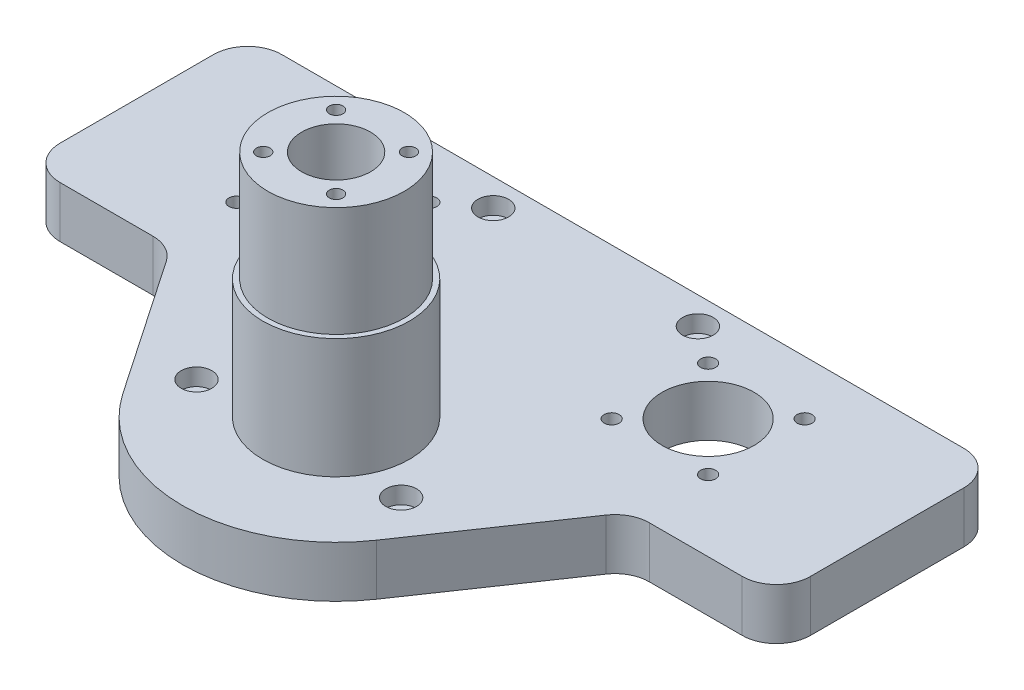
SolidWorks part; units mm, degrees
material "PLA Infill"
ref_plane "Front Plane" through (0, 0, 0) normal (0, 0, 1) x (1, 0, 0)
ref_plane "Top Plane" through (0, 0, 0) normal (0, 1, 0) x (1, 0, 0)
ref_plane "Right Plane" through (0, 0, 0) normal (1, 0, 0) x (0, 0, -1)
sketch "Sketch1" plane through (0, 0, 0) normal (0, 1, 0) x (1, 0, 0)
  line L0 (0, 0) -> (55, 54.0672) construction
  line L1 (55, 54.0672) -> (-55, 54.0672) construction
  line L2 (-55, 54.0672) -> (0, 0) construction
  line L3 (-79.7903, 37.1722) -> (-37.1854, -25.3425) construction
  line L4 (-55, 84.0672) -> (55, 84.0672)
  line L5 (37.1854, -25.3425) -> (79.7903, 37.1722) construction
  line L6 (-55, 84.0672) -> (-100, 84.0672)
  line L7 (-110, 74.0672) -> (-110, 29.0672)
  line L8 (-100, 19.0672) -> (-72.7378, 19.0672)
  line L9 (-64.4743, 14.6989) -> (-37.1854, -25.3425)
  line L10 (0, -1000) -> (0, 49000) construction
  line L11 (64.4743, 14.6989) -> (37.1854, -25.3425)
  line L12 (100, 19.0672) -> (72.7378, 19.0672)
  line L13 (110, 74.0672) -> (110, 29.0672)
  line L14 (55, 84.0672) -> (100, 84.0672)
  circle A0 centre (-55, 54.0672) radius 30 construction
  circle A1 centre (55, 54.0672) radius 30 construction
  circle A2 centre (0, 0) radius 45 construction
  arc A3 (-79.7903, 37.1722) -> (-55, 84.0672) centre (-55, 54.0672) cw construction
  arc A4 (55, 84.0672) -> (79.7903, 37.1722) centre (55, 54.0672) cw construction
  arc A5 (-37.1854, -25.3425) -> (37.1854, -25.3425) centre (0, 0) ccw
  arc A6 (-72.7378, 19.0672) -> (-64.4743, 14.6989) centre (-72.7378, 9.0672) cw
  arc A7 (-110, 29.0672) -> (-100, 19.0672) centre (-100, 29.0672) ccw
  arc A8 (-100, 84.0672) -> (-110, 74.0672) centre (-100, 74.0672) ccw
  arc A9 (72.7378, 19.0672) -> (64.4743, 14.6989) centre (72.7378, 9.0672) ccw
  arc A10 (110, 29.0672) -> (100, 19.0672) centre (100, 29.0672) cw
  arc A11 (100, 84.0672) -> (110, 74.0672) centre (100, 74.0672) cw
  point P23 (-67.4514, 19.0672)
  dimension "D3" = 60
  dimension "D4" = 90
  dimension "D5" = 10
  dimension "D6" = 55
  dimension "D1" = 110
  dimension "D2" = 77.125
  dimension "D7" = 35
extrude "Main Body" add sketch "Sketch1" along normal blind 15 contours A5 L11 A9 L12 A10 L13 A11 L14 L4 L6 A8 L7 A7 L8 A6 L9
sketch "Sketch3" plane through (0, 15, 0) normal (0, 1, 0) x (1, 0, 0)
  circle A0 centre (0, 0) radius 45 construction
  circle A1 centre (0, 0) radius 45 construction
  circle A2 centre (0, 0) radius 21.5
  dimension "D1" = 43
extrude "Front Extrusion" add sketch "Sketch3" along normal blind 67.3
sketch "Sketch4" plane through (0, 0, 0) normal (0, -1, 0) x (1, 0, 0)
  line L0 (0, -1000) -> (0, 49000) construction
  line L1 (-45, 0) -> (45, 0) construction
  line L2 (-85, -54.0672) -> (-25, -54.0672) construction
  line L3 (55, -54.0672) -> (-55, -54.0672) construction
  line L4 (-55, -24.0672) -> (-55, -84.0672) construction
  line L5 (-10.6773, 10.6773) -> (0, 0) construction
  line L6 (-10.6773, -10.6773) -> (0, 0) construction
  line L7 (-69.1421, -39.9251) -> (-55, -54.0672) construction
  line L8 (-100, -84.0672) -> (100, -84.0672) construction
  line L9 (100, -84.0672) -> (-100, -84.0672) construction
  line L10 (-30, -76.0672) -> (0, -76.0672) construction
  line L11 (-30, -76.0672) -> (-30, 10.9328) construction
  line L12 (-30, 10.9328) -> (0, 10.9328) construction
  line L13 (0, -76.0672) -> (0, 10.9328) construction
  circle A0 centre (55, -54.0672) radius 30 construction
  circle A1 centre (0, 0) radius 45 construction
  circle A2 centre (-55, -54.0672) radius 30 construction
  circle A3 centre (55, -54.0672) radius 30 construction
  circle A4 centre (0, 0) radius 45 construction
  circle A5 centre (-55, -54.0672) radius 30 construction
  circle A6 centre (0, 0) radius 10.1
  circle A7 centre (-55, -54.0672) radius 13.5
  circle A10 centre (-10.6773, 10.6773) radius 2
  circle A13 centre (-10.6773, -10.6773) radius 2
  circle A14 centre (-69.1421, -39.9251) radius 2.2
  circle A15 centre (-69.1421, -68.2094) radius 2.2
  circle A16 centre (-40.8579, -68.2094) radius 2.2
  circle A17 centre (-40.8579, -39.9251) radius 2.2
  circle A18 centre (55, -54.0672) radius 13.5
  circle A19 centre (69.1421, -68.2094) radius 2.2
  circle A20 centre (40.8579, -68.2094) radius 2.2
  circle A21 centre (40.8579, -39.9251) radius 2.2
  circle A22 centre (69.1421, -39.9251) radius 2.2
  circle A23 centre (10.6773, -10.6773) radius 2
  circle A24 centre (10.6773, 10.6773) radius 2
  circle A25 centre (-30, -76.0672) radius 2.5
  circle A26 centre (-30, 10.9328) radius 2.5
  circle A27 centre (30, -76.0672) radius 2.5
  circle A28 centre (30, 10.9328) radius 2.5
  dimension "D1" = 20.2
  dimension "D2" = 27
  dimension "D4" = 4
  dimension "D5" = 45
  dimension "D7" = 4.4
  dimension "D9" = 5
  dimension "D3" = 15.1
  dimension "D6" = 20
  dimension "D8" = 45
  dimension "D10" = 30
  dimension "D11" = 8
  dimension "D12" = 87
extrude "Bolt Holes" cut sketch "Sketch4" against normal through all
sketch "Sketch5" plane through (0, 0, 0) normal (0, -1, 0) x (1, 0, 0)
  line L0 (-14.92, 6.4347) -> (-9.9876, 1.5024)
  line L1 (-6.4347, 14.92) -> (-1.5024, 9.9876)
  line L2 (-10.6773, 10.6773) -> (0, 0) construction
  line L3 (-1000, 0) -> (49000, 0) construction
  line L4 (0, -1000) -> (0, 49000) construction
  line L5 (-14.92, -6.4347) -> (-9.9876, -1.5024)
  line L6 (-6.4347, -14.92) -> (-1.5024, -9.9876)
  line L7 (6.4347, -14.92) -> (1.5024, -9.9876)
  line L8 (14.92, -6.4347) -> (9.9876, -1.5024)
  line L9 (14.92, 6.4347) -> (9.9876, 1.5024)
  line L10 (6.4347, 14.92) -> (1.5024, 9.9876)
  circle A0 centre (-10.6773, 10.6773) radius 2 construction
  circle A1 centre (-10.6773, 10.6773) radius 6 construction
  circle A2 centre (0, 0) radius 10.1 construction
  arc A3 (-14.92, 6.4347) -> (-6.4347, 14.92) centre (-10.6773, 10.6773) cw
  circle A4 centre (0, 0) radius 10.1 construction
  arc A5 (-9.9876, 1.5024) -> (-1.5024, 9.9876) centre (0, 0) cw
  arc A6 (-14.92, -6.4347) -> (-6.4347, -14.92) centre (-10.6773, -10.6773) ccw
  arc A7 (-9.9876, -1.5024) -> (-1.5024, -9.9876) centre (0, 0) ccw
  arc A8 (14.92, -6.4347) -> (6.4347, -14.92) centre (10.6773, -10.6773) cw
  arc A9 (9.9876, -1.5024) -> (1.5024, -9.9876) centre (0, 0) cw
  arc A10 (14.92, 6.4347) -> (6.4347, 14.92) centre (10.6773, 10.6773) ccw
  arc A11 (9.9876, 1.5024) -> (1.5024, 9.9876) centre (0, 0) ccw
  dimension "D1" = 4
  dimension "D2" = 4
extrude "Bolt Recesses Rear" cut sketch "Sketch5" against normal blind 10
sketch "Sketch6" plane through (0, 15, 0) normal (0, 1, 0) x (1, 0, 0)
  circle A1 centre (30, 76.0672) radius 4.5
  circle A2 centre (-30, -10.9328) radius 2.5 construction
  circle A3 centre (30, -10.9328) radius 2.5 construction
  circle A4 centre (30, 76.0672) radius 2.5 construction
  circle A5 centre (-30, 76.0672) radius 2.5 construction
  circle A6 centre (-30, -10.9328) radius 2.5 construction
  circle A7 centre (30, -10.9328) radius 2.5 construction
  circle A8 centre (30, 76.0672) radius 2.5 construction
  circle A9 centre (-30, 76.0672) radius 2.5 construction
  circle A10 centre (-30, 76.0672) radius 4.5
  circle A11 centre (-30, -10.9328) radius 4.5
  circle A12 centre (30, -10.9328) radius 4.5
  dimension "D1" = 9
extrude "Bolt Recesses Front" cut sketch "Sketch6" against normal blind 5
ref_plane "First Bearing Section" through (0, 50.1, 0) normal (0, 1, 0) x (1, 0, 0)
sketch "Sketch7" plane through (0, 82.3, 0) normal (0, 1, 0) x (1, 0, 0)
  circle A0 centre (0, 0) radius 21.5 construction
  circle A1 centre (0, 0) radius 21.5
  circle A2 centre (0, 0) radius 20
  dimension "D1" = 40
extrude "Cut-Extrude1" cut sketch "Sketch7" against normal up to surface (32.2 mm away) up to plane "First Bearing Section"
sketch "Sketch8" plane through (0, 0, 0) normal (0, -1, 0) x (1, 0, 0)
  line L0 (0, -1000) -> (0, 49000) construction
  circle A0 centre (-69.1421, -68.2094) radius 2.2 construction
  circle A1 centre (-40.8579, -68.2094) radius 2.2 construction
  circle A2 centre (-40.8579, -39.9251) radius 2.2 construction
  circle A3 centre (-69.1421, -39.9251) radius 2.2 construction
  circle A4 centre (-69.1421, -68.2094) radius 2.2 construction
  circle A5 centre (-40.8579, -68.2094) radius 2.2 construction
  circle A6 centre (-40.8579, -39.9251) radius 2.2 construction
  circle A7 centre (-69.1421, -39.9251) radius 2.2 construction
  circle A8 centre (-69.1421, -39.9251) radius 3.25
  circle A9 centre (-40.8579, -39.9251) radius 3.25
  circle A10 centre (-40.8579, -68.2094) radius 3.25
  circle A11 centre (-69.1421, -68.2094) radius 3.25
  circle A12 centre (40.8579, -68.2094) radius 3.25
  circle A13 centre (40.8579, -39.9251) radius 3.25
  circle A14 centre (69.1421, -68.2094) radius 3.25
  circle A15 centre (69.1421, -39.9251) radius 3.25
  dimension "D1" = 6.5
extrude "Motor bolt head recesses" cut sketch "Sketch8" against normal blind 6
sketch "Sketch9" plane through (0, 0, 0) normal (0, -1, 0) x (1, 0, 0)
  line L0 (0, -1000) -> (0, 49000) construction
  line L1 (-110, -74.0672) -> (-110, -29.0672) construction
  line L2 (100, -84.0672) -> (-100, -84.0672) construction
  line L4 (-106, -74.0672) -> (-44, -74.0672) construction
  line L5 (-106, -74.0672) -> (-106, -32.0672) construction
  line L6 (-106, -32.0672) -> (-44, -32.0672) construction
  line L7 (-44, -74.0672) -> (-44, -32.0672) construction
  circle A0 centre (-106, -74.0672) radius 2
  circle A1 centre (-106, -32.0672) radius 2
  circle A2 centre (-44, -32.0672) radius 2
  circle A3 centre (-44, -74.0672) radius 2
  circle A4 centre (44, -74.0672) radius 2
  circle A5 centre (106, -74.0672) radius 2
  circle A6 centre (44, -32.0672) radius 2
  circle A7 centre (106, -32.0672) radius 2
  dimension "D3" = 4
  dimension "D1" = 4
  dimension "D2" = 10
  dimension "D4" = 62
  dimension "D5" = 42
extrude "Heat-set insert holes" cut sketch "Sketch9" against normal blind 6
